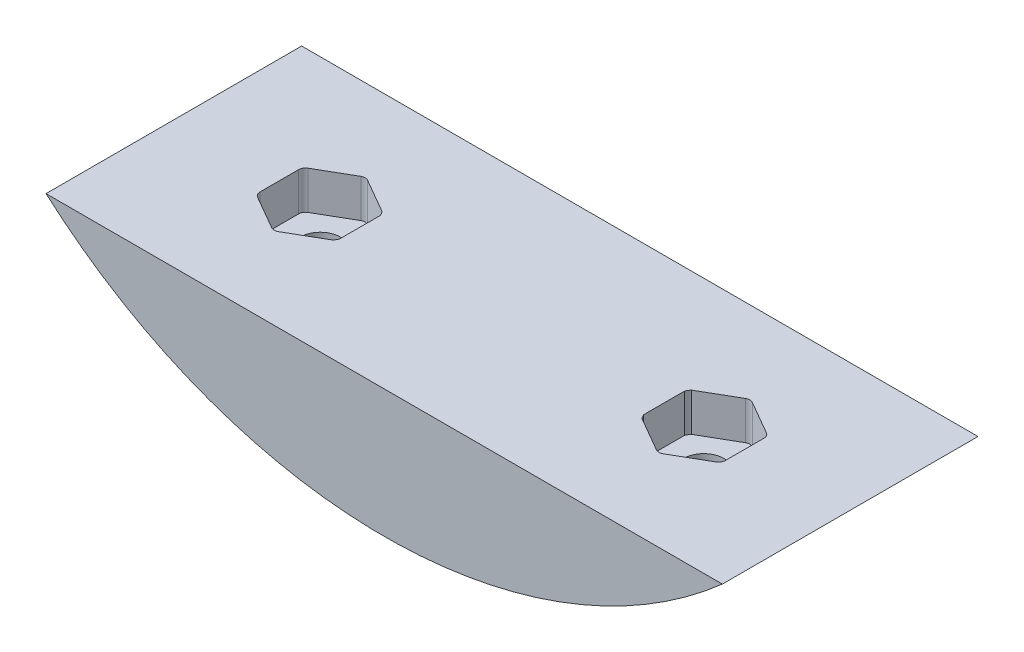
SolidWorks part; units mm, degrees
material "ABS"
ref_plane "Front Plane" through (0, 0, 0) normal (0, 0, 1) x (1, 0, 0)
ref_plane "Top Plane" through (0, 0, 0) normal (0, 1, 0) x (1, 0, 0)
ref_plane "Right Plane" through (0, 0, 0) normal (1, 0, 0) x (0, 0, -1)
sketch "Sketch1" plane through (0, 0, 0) normal (0, 0, 1) x (1, 0, 0)
  line L0 (0, 0) -> (67.2021, 0)
  arc A0 (0, 0) -> (67.2021, 0) centre (33.601, 38.1) ccw
  dimension "D1" = 50.8
  dimension "D2" = 38.1
extrude "Boss-Extrude1" add sketch "Sketch1" along normal blind 25.4
sketch "Sketch2" plane through (0, 0, 0) normal (0, 1, 0) x (1, 0, 0)
  line L0 (0, -12.7) -> (14.551, -12.7) construction
  line L1 (0, -25.4) -> (0, 0) construction
  line L2 (14.551, -12.7) -> (52.651, -12.7) construction
  line L3 (52.651, -12.7) -> (67.2021, -12.7) construction
  line L4 (67.2021, -25.4) -> (67.2021, 0) construction
  circle A0 centre (14.551, -12.7) radius 2
  circle A1 centre (52.651, -12.7) radius 2
  dimension "D2" = 4
  dimension "D1" = 38.1
extrude "Cut-Extrude1" cut sketch "Sketch2" against normal through all both and the other way through all
sketch "Sketch3" plane through (0, 0, 0) normal (0, 1, 0) x (1, 0, 0)
  line L0 (16.2867, -9.6973) -> (14.575, -8.7091) construction
  line L1 (14.4, -8.7091) -> (12.7867, -9.6405) construction
  line L2 (17.9875, -14.6197) -> (17.9875, -12.7) construction
  line L3 (17.9875, -12.7) -> (17.9875, -10.7803) construction
  line L4 (17.9, -10.6288) -> (16.2867, -9.6973) construction
  line L5 (12.7867, -9.6405) -> (11.075, -10.6288) construction
  line L6 (10.9875, -10.7803) -> (10.9875, -12.7) construction
  line L7 (16.2867, -15.7027) -> (17.9, -14.7712) construction
  line L8 (14.575, -16.6909) -> (16.2867, -15.7027) construction
  line L9 (12.7867, -15.7595) -> (14.4, -16.6909) construction
  line L10 (11.075, -14.7712) -> (12.7867, -15.7595) construction
  line L11 (10.9875, -12.7) -> (10.9875, -14.6197) construction
  line L12 (33.601, 0) -> (33.601, -25.4) construction
  line L13 (67.2021, 0) -> (0, 0) construction
  line L14 (67.2021, -25.4) -> (0, -25.4) construction
  line L15 (10.9875, -12.7) -> (17.9875, -12.7) construction
  line L16 (16.2867, -9.6973) -> (12.7867, -15.7595) construction
  line L17 (12.7867, -9.6405) -> (16.2867, -15.7027) construction
  line L18 (16.7867, -8.8313) -> (15.075, -7.843) construction
  line L19 (13.9, -7.843) -> (12.2867, -8.7745) construction
  line L20 (12.2867, -8.7745) -> (10.575, -9.7627) construction
  line L21 (9.9875, -10.7803) -> (9.9875, -12.7) construction
  line L22 (9.9875, -12.7) -> (9.9875, -14.6197) construction
  line L23 (10.575, -15.6373) -> (12.2867, -16.6255) construction
  line L24 (12.2867, -16.6255) -> (13.9, -17.557) construction
  line L25 (15.075, -17.557) -> (16.7867, -16.5687) construction
  line L26 (16.7867, -16.5687) -> (18.5664, -15.5412) construction
  line L27 (18.9875, -14.8119) -> (18.9875, -12.7) construction
  line L28 (18.9875, -12.7) -> (18.9875, -10.5881) construction
  line L29 (18.5664, -9.8588) -> (16.7867, -8.8313) construction
  line L30 (56.7146, -12.7) -> (56.7146, -14.6197)
  line L31 (56.7146, -10.7803) -> (56.7146, -12.7)
  line L32 (54.6654, -9.2075) -> (56.3771, -10.1957)
  line L57 (14.551, -10.7) -> (14.551, -14.7) construction
  line L58 (14.551, -14.7) -> (16.551, -12.7) construction
  line L59 (16.551, -12.7) -> (12.551, -12.7) construction
  line L60 (10.825, -15.2043) -> (12.5367, -16.1925)
  line L61 (12.5367, -16.1925) -> (14.15, -17.1239)
  line L62 (14.825, -17.1239) -> (16.5367, -16.1357)
  line L63 (16.5367, -16.1357) -> (18.2398, -15.1524)
  line L64 (18.4875, -14.7233) -> (18.4875, -12.7)
  line L65 (18.4875, -12.7) -> (18.4875, -10.6767)
  line L66 (18.2398, -10.2476) -> (16.5367, -9.2643)
  line L67 (16.5367, -9.2643) -> (14.825, -8.2761)
  line L68 (14.15, -8.2761) -> (12.5367, -9.2075)
  line L69 (12.5367, -9.2075) -> (10.825, -10.1957)
  line L70 (10.4875, -10.7803) -> (10.4875, -12.7)
  line L71 (10.4875, -12.7) -> (10.4875, -14.6197)
  line L72 (53.0521, -8.2761) -> (54.6654, -9.2075)
  line L73 (50.6654, -9.2643) -> (52.3771, -8.2761)
  line L74 (48.9623, -10.2476) -> (50.6654, -9.2643)
  line L75 (48.7146, -12.7) -> (48.7146, -10.6767)
  line L76 (48.7146, -14.7233) -> (48.7146, -12.7)
  line L77 (50.6654, -16.1357) -> (48.9623, -15.1524)
  line L78 (52.3771, -17.1239) -> (50.6654, -16.1357)
  line L79 (54.6654, -16.1925) -> (53.0521, -17.1239)
  line L80 (56.3771, -15.2043) -> (54.6654, -16.1925)
  arc A2 (14.575, -8.7091) -> (14.4, -8.7091) centre (14.4875, -8.8606) ccw construction
  arc A3 (17.9875, -10.7803) -> (17.9, -10.6288) centre (16.929, -11.2904) ccw construction
  arc A4 (11.075, -10.6288) -> (10.9875, -10.7803) centre (11.1625, -10.7803) ccw construction
  arc A5 (17.9, -14.7712) -> (17.9875, -14.6197) centre (16.929, -14.1096) ccw construction
  arc A6 (14.4, -16.6909) -> (14.575, -16.6909) centre (14.4875, -16.5394) ccw construction
  arc A7 (10.9875, -14.6197) -> (11.075, -14.7712) centre (11.1625, -14.6197) ccw construction
  arc A8 (15.075, -7.843) -> (13.9, -7.843) centre (14.4875, -8.8606) ccw construction
  arc A9 (10.575, -9.7627) -> (9.9875, -10.7803) centre (11.1625, -10.7803) ccw construction
  arc A10 (9.9875, -14.6197) -> (10.575, -15.6373) centre (11.1625, -14.6197) ccw construction
  arc A11 (13.9, -17.557) -> (15.075, -17.557) centre (14.4875, -16.5394) ccw construction
  arc A12 (18.5664, -15.5412) -> (18.9875, -14.8119) centre (16.929, -14.1096) ccw construction
  arc A13 (18.9875, -10.5881) -> (18.5664, -9.8588) centre (16.929, -11.2904) ccw construction
  circle A26 centre (14.551, -12.7) radius 2 construction
  circle A27 centre (14.551, -12.7) radius 2 construction
  arc A28 (14.15, -17.1239) -> (14.825, -17.1239) centre (14.4875, -16.5394) ccw
  arc A29 (18.2398, -15.1524) -> (18.4875, -14.7233) centre (16.929, -14.1096) ccw
  arc A30 (18.4875, -10.6767) -> (18.2398, -10.2476) centre (16.929, -11.2904) ccw
  arc A31 (14.825, -8.2761) -> (14.15, -8.2761) centre (14.4875, -8.8606) ccw
  arc A32 (10.825, -10.1957) -> (10.4875, -10.7803) centre (11.1625, -10.7803) ccw
  arc A33 (10.4875, -14.6197) -> (10.825, -15.2043) centre (11.1625, -14.6197) ccw
  arc A34 (56.7146, -14.6197) -> (56.3771, -15.2043) centre (56.0396, -14.6197) cw
  arc A35 (56.3771, -10.1957) -> (56.7146, -10.7803) centre (56.0396, -10.7803) cw
  arc A36 (52.3771, -8.2761) -> (53.0521, -8.2761) centre (52.7146, -8.8606) cw
  arc A37 (48.7146, -10.6767) -> (48.9623, -10.2476) centre (50.2731, -11.2904) cw
  arc A38 (48.9623, -15.1524) -> (48.7146, -14.7233) centre (50.2731, -14.1096) cw
  arc A39 (53.0521, -17.1239) -> (52.3771, -17.1239) centre (52.7146, -16.5394) cw
  dimension "D1" = 0.5
extrude "Cut-Extrude2" cut sketch "Sketch3" against normal blind 3.81
